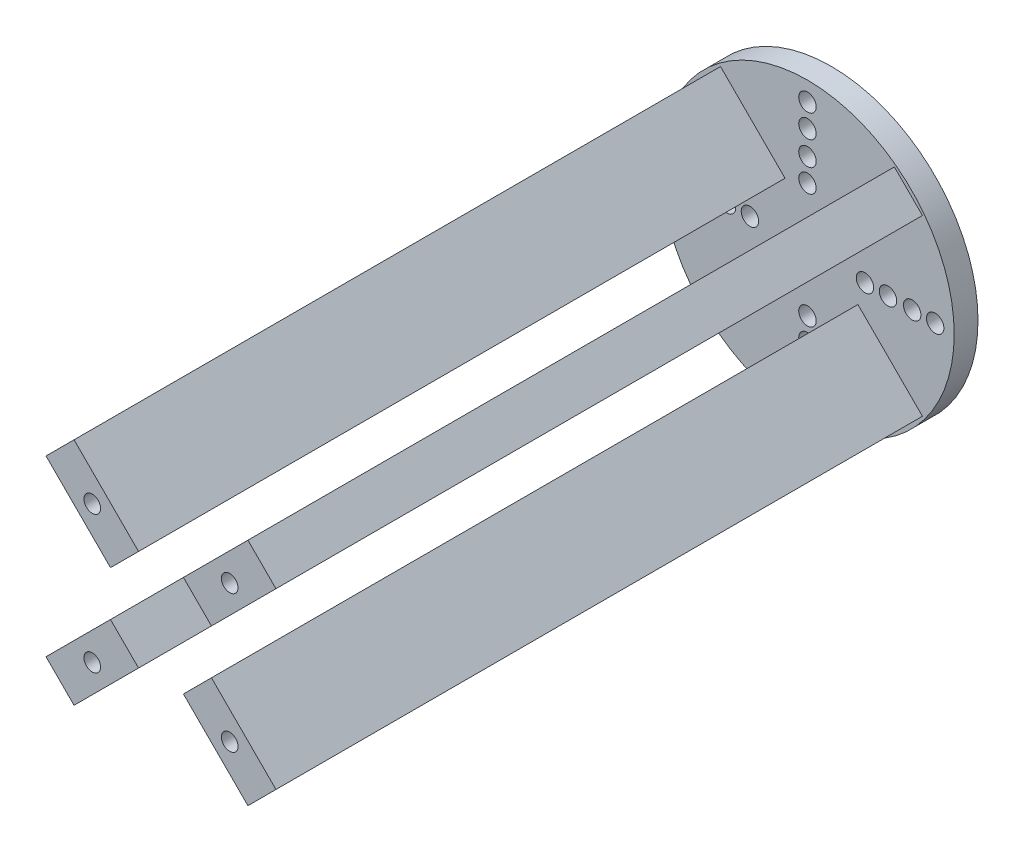
SolidWorks part; units mm, degrees
ref_plane "Ebene vorne" through (0, 0, 0) normal (0, 0, 1) x (1, 0, 0)
ref_plane "Ebene oben" through (0, 0, 0) normal (0, 1, 0) x (1, 0, 0)
ref_plane "Ebene rechts" through (0, 0, 0) normal (1, 0, 0) x (0, 0, -1)
sketch "Skizze2" plane through (0, 0, 0) normal (0, 0, 1) x (1, 0, 0)
  line L0 (0, 18.5) -> (0, -18.5)
  line L1 (-18.5, 0) -> (18.5, 0)
  circle A0 centre (0, 0) radius 18.5
  arc A1 (16.0624, -1.0994) -> (16.0624, 1.0994) centre (0, 0) ccw
  arc A2 (13.1542, -1.099) -> (13.1542, 1.099) centre (0, 0) ccw
  arc A3 (10.0904, -1.0984) -> (10.0904, 1.0984) centre (0, 0) ccw
  arc A4 (7.1666, -1.0968) -> (7.1666, 1.0968) centre (0, 0) ccw
  circle A5 centre (0, 7.25) radius 1.1
  circle A6 centre (0, 10.15) radius 1.1
  circle A7 centre (0, 13.2) radius 1.1
  circle A8 centre (0, 16.1) radius 1.1
  circle A9 centre (7.25, 0) radius 1.1
  circle A10 centre (10.15, 0) radius 1.1
  circle A11 centre (13.2, 0) radius 1.1
  circle A12 centre (16.1, 0) radius 1.1
  circle A13 centre (0, -7.25) radius 1.1
  circle A14 centre (0, -10.15) radius 1.1
  circle A15 centre (0, -13.2) radius 1.1
  circle A16 centre (0, -16.1) radius 1.1
  circle A17 centre (-7.25, 0) radius 1.1
  circle A18 centre (-10.15, 0) radius 1.1
  circle A19 centre (-13.2, 0) radius 1.1
  circle A20 centre (-16.1, 0) radius 1.1
  arc A21 (1.0968, 7.1666) -> (-1.0968, 7.1666) centre (0, 0) ccw
  arc A22 (1.0984, 10.0904) -> (-1.0984, 10.0904) centre (0, 0) ccw
  arc A23 (1.099, 13.1542) -> (-1.099, 13.1542) centre (0, 0) ccw
  arc A24 (1.0994, 16.0624) -> (-1.0994, 16.0624) centre (0, 0) ccw
  arc A25 (-7.1666, 1.0968) -> (-7.1666, -1.0968) centre (0, 0) ccw
  arc A26 (-10.0904, 1.0984) -> (-10.0904, -1.0984) centre (0, 0) ccw
  arc A27 (-13.1542, 1.099) -> (-13.1542, -1.099) centre (0, 0) ccw
  arc A28 (-16.0624, 1.0994) -> (-16.0624, -1.0994) centre (0, 0) ccw
  arc A29 (-1.0968, -7.1666) -> (1.0968, -7.1666) centre (0, 0) ccw
  arc A30 (-1.0984, -10.0904) -> (1.0984, -10.0904) centre (0, 0) ccw
  arc A31 (-1.099, -13.1542) -> (1.099, -13.1542) centre (0, 0) ccw
  arc A32 (-1.0994, -16.0624) -> (1.0994, -16.0624) centre (0, 0) ccw
  point P46 (0, 0)
  dimension "D1" = 37
  dimension "D2" = 32.2
  dimension "D3" = 26.4
  dimension "D4" = 20.3
  dimension "D5" = 14.5
  dimension "D6" = 2.2
  dimension "D7" = 4
extrude "Aufsatz-Linear austragen1" add sketch "Skizze2" along normal blind 3 contours A12 L1 A0 L0 A8 A7 A6 A5 A9 A10 A11 | A16 L0 A0 L1 A12 A11 A10 A9 A13 A14 A15 | A20 L1 A0 L0 A16 A15 A14 A13 A17 A18 A19 | A20 L1 A19 A18 A17 L0 A5 A6 A7 A8 A0 region at (7.9584, 7.9584, 0) region at (-7.9584, 7.9584, 0) region at (7.9584, -7.9584, 0) region at (-7.9584, -7.9584, 0)
sketch "Skizze4" plane through (0, 0, 3) normal (0, 0, 1) x (1, 0, 0)
  line L0 (0, 0) -> (13.0815, 13.0815) construction
  line L1 (2.8284, 6.364) -> (10.9602, 14.4957)
  line L2 (2.8284, 6.364) -> (6.364, 2.8284)
  line L3 (10.9602, 14.4957) -> (14.4957, 10.9602)
  line L4 (6.364, 2.8284) -> (14.4957, 10.9602)
  line L5 (0, 0) -> (18.5, 0) construction
  line L6 (6.364, -2.8284) -> (14.4957, -10.9602)
  line L7 (6.364, -2.8284) -> (2.8284, -6.364)
  line L8 (2.8284, -6.364) -> (10.9602, -14.4957)
  line L9 (14.4957, -10.9602) -> (10.9602, -14.4957)
  line L10 (-2.8284, -6.364) -> (-10.9602, -14.4957)
  line L11 (-2.8284, -6.364) -> (-6.364, -2.8284)
  line L12 (-6.364, -2.8284) -> (-14.4957, -10.9602)
  line L13 (-10.9602, -14.4957) -> (-14.4957, -10.9602)
  line L14 (-6.364, 2.8284) -> (-14.4957, 10.9602)
  line L15 (-6.364, 2.8284) -> (-2.8284, 6.364)
  line L16 (-2.8284, 6.364) -> (-10.9602, 14.4957)
  line L17 (-14.4957, 10.9602) -> (-10.9602, 14.4957)
  circle A0 centre (0, 0) radius 18.5 construction
  point P26 (0, 0)
  dimension "D1" = 2.5
  dimension "D2" = 45
  dimension "D3" = 11.5
  dimension "D4" = 6.5
  dimension "D5" = 2.5
  dimension "D6" = 4
extrude "Aufsatz-Linear austragen2" add sketch "Skizze4" along normal blind 81.5
sketch "Skizze5" plane through (0, 0, 84.5) normal (0, 0, 1) x (1, 0, 0)
  line L0 (-6.364, -2.8284) -> (-10.9602, -14.4957) construction
  line L1 (-2.8284, -6.364) -> (-6.364, -2.8284) construction
  line L2 (-6.364, -2.8284) -> (-14.4957, -10.9602) construction
  line L3 (-10.9602, -14.4957) -> (-14.4957, -10.9602) construction
  line L4 (-2.8284, -6.364) -> (-14.4957, -10.9602) construction
  circle A0 centre (-8.6621, -8.6621) radius 1.05
  circle A1 centre (-8.6621, 8.6621) radius 1.05
  circle A2 centre (8.6621, 8.6621) radius 1.05
  circle A3 centre (8.6621, -8.6621) radius 1.05
  point P22 (0, 0)
  dimension "D1" = 2.1
  dimension "D2" = 4
extrude "Schnitt-Linear austragen2" cut sketch "Skizze5" against normal blind 13
